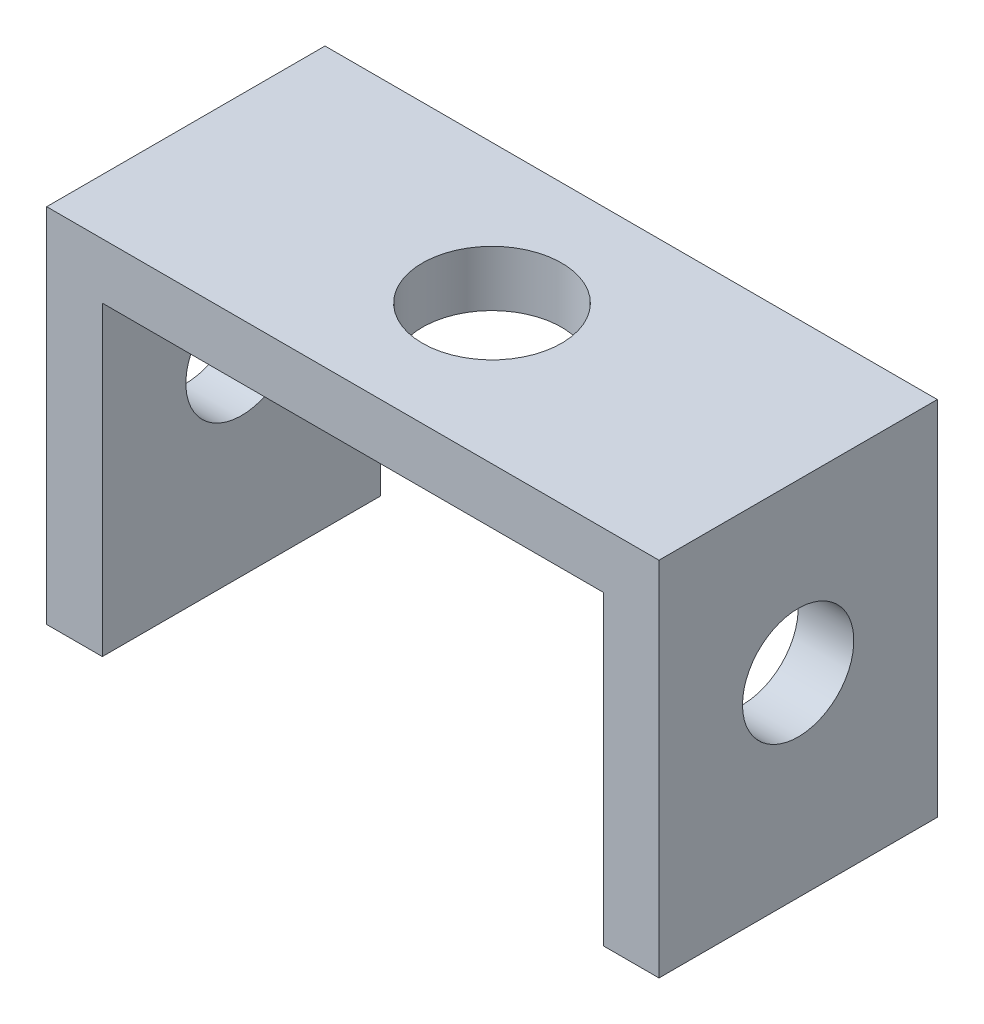
SolidWorks part; units mm, degrees
ref_plane "Front Plane" through (0, 0, 0) normal (0, 0, 1) x (1, 0, 0)
ref_plane "Top Plane" through (0, 0, 0) normal (0, 1, 0) x (1, 0, 0)
ref_plane "Right Plane" through (0, 0, 0) normal (1, 0, 0) x (0, 0, -1)
sketch "Sketch1" plane through (0, 0, 0) normal (0, 1, 0) x (1, 0, 0)
  line L1 (-55, 25) -> (55, 25)
  line L2 (-55, 25) -> (-55, -25)
  line L3 (-55, -25) -> (55, -25)
  line L4 (55, 25) -> (55, -25)
  circle A0 centre (0, 0) radius 12.5
  dimension "D1" = 25
  dimension "D2" = 50
  dimension "D3" = 110
  dimension "D4" = 55
  dimension "D5" = 25
extrude "Boss-Extrude1" add sketch "Sketch1" along normal blind 10
sketch "Sketch2" plane through (0, 0, 0) normal (1, 0, 0) x (0, 0, -1)
  line L1 (-25, 10) -> (25, 10)
  line L2 (-25, 10) -> (-25, -55)
  line L3 (-25, -55) -> (25, -55)
  line L4 (25, 10) -> (25, -55)
  circle A0 centre (0, -20) radius 10
  point P7 (0, 0)
  dimension "D3" = 20
  dimension "D1" = 65
  dimension "D2" = 50
  dimension "D4" = 30
extrude "Boss-Extrude2" add sketch "Sketch2" against normal blind 10 from surface starting at face at (55, 5, 0)
extrude "Boss-Extrude3" add sketch "Sketch2<2>" along normal blind 10 from surface starting at face at (-55, 5, 0)
sketch "Sketch2<2>" plane through (0, 0, 0) normal (1, 0, 0) x (0, 0, -1) same geometry as "Sketch2"
